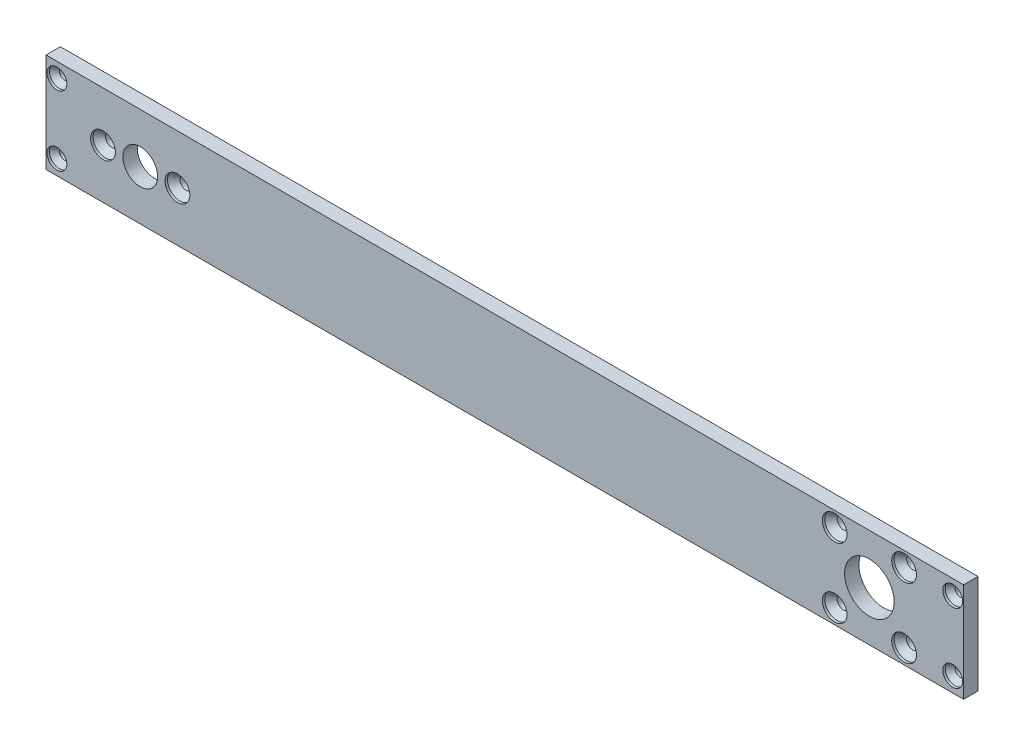
SolidWorks part; units mm, degrees
ref_plane "Front Plane" through (0, 0, 0) normal (0, 0, 1) x (1, 0, 0)
ref_plane "Top Plane" through (0, 0, 0) normal (0, 1, 0) x (1, 0, 0)
ref_plane "Right Plane" through (0, 0, 0) normal (1, 0, 0) x (0, 0, -1)
sketch "Sketch1" plane through (0, 0, 0) normal (0, 0, 1) x (1, 0, 0)
  line L1 (-92.5, 10) -> (92.5, 10)
  line L2 (-92.5, 10) -> (-92.5, -10)
  line L3 (-92.5, -10) -> (92.5, -10)
  line L4 (92.5, 10) -> (92.5, -10)
  line L5 (-92.5, 10) -> (92.5, -10) construction
  line L6 (-92.5, -10) -> (92.5, 10) construction
  point P0 (0, 0)
  dimension "D1" = 20
  dimension "D2" = 185
extrude "Base shape" add sketch "Sketch1" against normal blind 2.9
sketch "Sketch2" plane through (0, 0, 0) normal (0, 0, 1) x (1, 0, 0)
  line L0 (-83.5, 10) -> (-83.5, -10) construction
  line L1 (92.5, 10) -> (-92.5, 10) construction
  line L2 (-92.5, -10) -> (92.5, -10) construction
  line L3 (-92.5, 10) -> (-92.5, -10) construction
  line L4 (-92.5, 0) -> (92.5, 0) construction
  line L5 (92.5, -10) -> (92.5, 10) construction
  line L6 (-73.5, 10) -> (-73.5, -10) construction
  line L7 (0, 10) -> (0, -10) construction
  line L8 (73.5, 5) -> (92.5, 5) construction
  line L9 (-73.5, 3.5) -> (-92.5, 3.5) construction
  line L11 (80.5, -7) -> (66.5, -7)
  line L12 (80.5, -7) -> (80.5, 7)
  line L13 (80.5, 7) -> (66.5, 7)
  line L14 (66.5, -7) -> (66.5, 7)
  line L15 (80.5, -7) -> (66.5, 7) construction
  line L16 (80.5, 7) -> (66.5, -7) construction
  circle A0 centre (-73.5, 0) radius 10
  circle A1 centre (-81, 0) radius 1.25
  circle A2 centre (-66, 0) radius 1.25
  circle A3 centre (-73.5, 0) radius 3.5
  circle A4 centre (73.5, 0) radius 5
  circle A5 centre (66.5, 7) radius 1.25
  circle A6 centre (80.5, 7) radius 1.25
  circle A7 centre (80.5, -7) radius 1.25
  circle A8 centre (66.5, -7) radius 1.25
  dimension "D2" = 20
  dimension "D3" = 2.5
  dimension "D4" = 15
  dimension "D5" = 7
  dimension "D6" = 10
  dimension "D8" = 2.5
  dimension "D1" = 147
  dimension "D7" = 14
extrude "Motor cutouts" cut sketch "Sketch2" against normal up to next contours A5 | A6 | A7 | A8 | A1 | A2 | A3 | A4
hole_wizard "Motor M2.5 countersunks" positions "Sketch3" profile "Sketch4" countersink size "M2.5" standard "ANSI Metric" end condition through all
sketch "Sketch3" plane through (0, 0, 0) normal (0, 0, 1) x (1, 0, 0)
  point P0 (-81, 0)
  point P3 (-66, 0)
  point P7 (66.5, 7)
  point P10 (80.5, 7)
  point P13 (66.5, -7)
  point P16 (80.5, -7)
sketch "Sketch4" plane through (-81, 0, 0) normal (1, 0, 0) x (0, -1, 0)
  line L0 (0, 0) -> (0, 2.9)
  line L1 (0, 2.9) -> (1.25, 2.9)
  line L2 (1.25, 2.9) -> (1.25, 1.75)
  line L3 (1.25, 1.75) -> (2.5, 0.5)
  line L4 (2.5, 0.5) -> (2.5, 0)
  line L6 (2.5, 0) -> (0, 0)
  line L7 (-1.25, 1.75) -> (-2.5, 0.5) construction
  line L11 (0, -6.35) -> (0, 107.95) construction
  dimension "Thru Hole Dia." = 2.5
  dimension "Thru Hole Depth" = 2.9
  dimension "C'Sink Dia." = 5
  dimension "C'Sink Angle" = 90
  dimension "Head Clearance" = 0.5
sketch "Sketch5" plane through (0, 0, -2.9) normal (0, 0, -1) x (-1, 0, 0)
  line L0 (0, 10) -> (0, -10) construction
  line L3 (-92.5, 10) -> (92.5, 10) construction
  line L4 (92.5, -10) -> (-92.5, -10) construction
  line L5 (-60, -7) -> (60, -7) construction
  line L6 (-60, -6) -> (60, -6)
  line L7 (-60, -8) -> (60, -8)
  arc A0 (-60, -6) -> (-60, -8) centre (-60, -7) ccw
  arc A1 (60, -8) -> (60, -6) centre (60, -7) ccw
  point P8 (0, -7)
  dimension "D1" = 120
  dimension "D2" = 2
  dimension "D3" = 2
extrude "PCB slot" cut sketch "Sketch5" against normal blind 0.775
sketch "Sketch6" plane through (0, 0, 0) normal (0, 0, 1) x (1, 0, 0)
  line L0 (90.3, 10) -> (90.3, -10) construction
  line L1 (92.5, 10) -> (-92.5, 10) construction
  line L2 (-92.5, -10) -> (92.5, -10) construction
  line L3 (92.5, -10) -> (92.5, 10) construction
  line L4 (92.5, 0) -> (-92.5, 0) construction
  line L5 (-92.5, 10) -> (-92.5, -10) construction
  line L6 (0, 10) -> (0, -10) construction
  circle A0 centre (90.3, 7) radius 1
  circle A2 centre (90.3, -7) radius 1
  circle A3 centre (-90.3, -7) radius 1
  circle A5 centre (-90.3, 7) radius 1
  dimension "D2" = 2
  dimension "D1" = 2.2
  dimension "D3" = 14
extrude "End plate holes" cut sketch "Sketch6" against normal up to next
hole_wizard "CSK for M2 Flat Head Machine Screw3" positions "Sketch10" profile "Sketch9" countersink size "M2" standard "ANSI Metric" end condition through all
sketch "Sketch10" plane through (0, 0, 0) normal (0, 0, 1) x (1, 0, 0)
  point P2 (90.3, 7)
  point P8 (90.3, -7)
  point P11 (-90.3, 7)
  point P17 (-90.3, -7)
  point P23 (0, 0)
  point P24 (0, 0)
sketch "Sketch9" plane through (90.3, 7, 0) normal (1, 0, 0) x (0, -1, 0)
  line L0 (0, 0) -> (0, 2.9)
  line L1 (0, 2.9) -> (1, 2.9)
  line L2 (1, 2.9) -> (1, 1.5)
  line L3 (1, 1.5) -> (2, 0.5)
  line L4 (2, 0.5) -> (2, 0)
  line L6 (2, 0) -> (0, 0)
  line L7 (-1, 1.5) -> (-2, 0.5) construction
  line L11 (0, -6.35) -> (0, 107.95) construction
  dimension "Thru Hole Dia." = 2
  dimension "Thru Hole Depth" = 2.9
  dimension "C'Sink Dia." = 4
  dimension "C'Sink Angle" = 90
  dimension "Head Clearance" = 0.5
